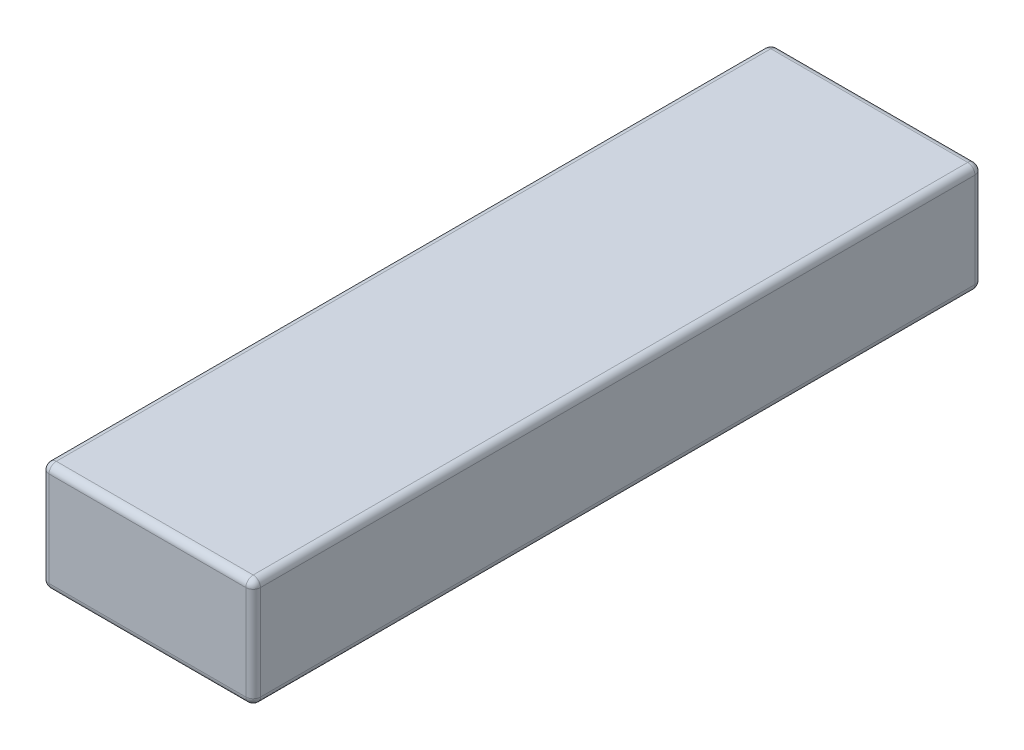
SolidWorks part; units mm, degrees
ref_plane "Front Plane" through (0, 0, 0) normal (0, 0, 1) x (1, 0, 0)
ref_plane "Top Plane" through (0, 0, 0) normal (0, 1, 0) x (1, 0, 0)
ref_plane "Right Plane" through (0, 0, 0) normal (1, 0, 0) x (0, 0, -1)
sketch "Sketch1" plane through (0, 0, 0) normal (0, 1, 0) x (1, 0, 0)
  line L1 (-29, -100) -> (29, -100)
  line L2 (-29, -100) -> (-29, 100)
  line L3 (-29, 100) -> (29, 100)
  line L4 (29, -100) -> (29, 100)
  line L5 (-29, -100) -> (29, 100) construction
  line L6 (-29, 100) -> (29, -100) construction
  point P0 (0, 0)
  dimension "D1" = 58
  dimension "D2" = 200
extrude "Boss-Extrude1" add sketch "Sketch1" along normal blind 30
fillet "Fillet1" radius 2 9 edges at (-29, 0, 0) (0, 0, 100) (29, 30, 0) (0, 30, -100) (-29, 30, 0) (0, 30, 100) (29, 15, 100) (-29, 15, 100) (-29, 15, -100)
fillet "Fillet2" radius 2 6 edges at (-28.4142, 0.5858, -99.4142) (28.4142, 0.5858, 99.4142) (28.4142, 29.4142, -99.4142) (1, 0, -100) (29, 0, -1) (29, 14, -100)
